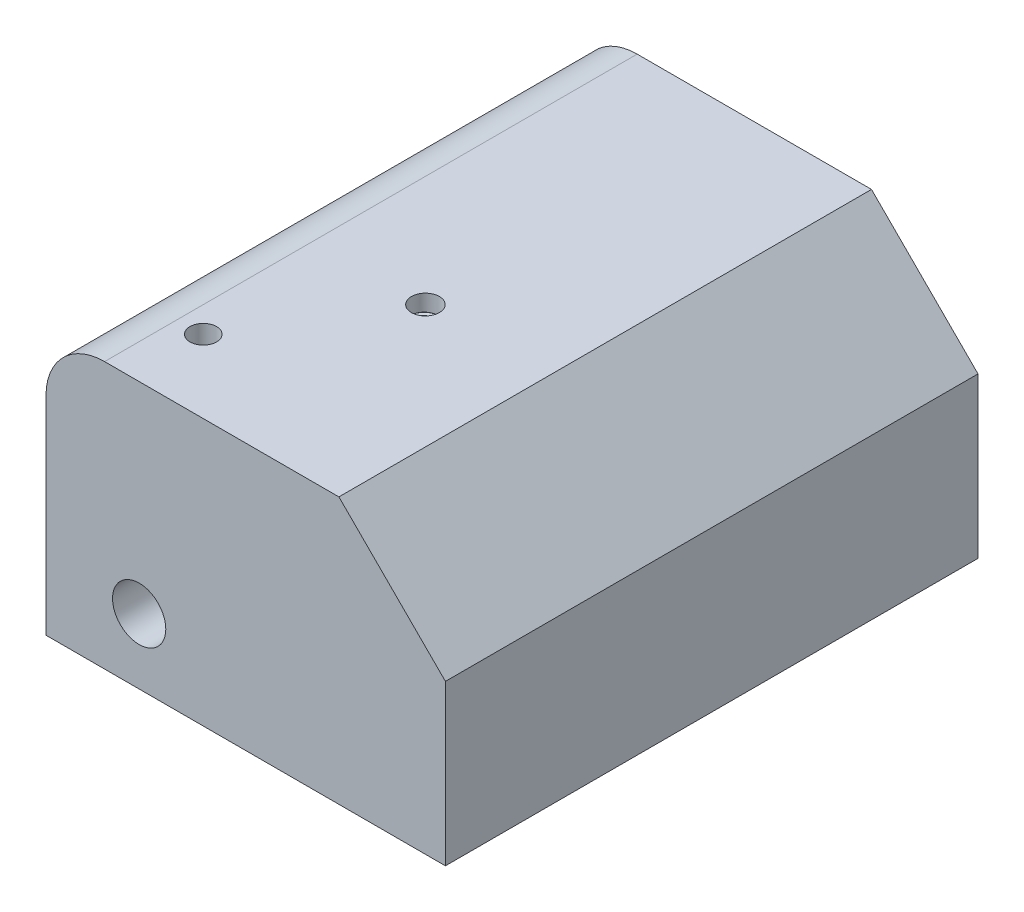
SolidWorks part; units mm, degrees
ref_plane "Front Plane" through (0, 0, 0) normal (0, 0, 1) x (1, 0, 0)
ref_plane "Top Plane" through (0, 0, 0) normal (0, 1, 0) x (1, 0, 0)
ref_plane "Right Plane" through (0, 0, 0) normal (1, 0, 0) x (0, 0, -1)
sketch "Sketch1" plane through (0, 0, 0) normal (0, 0, 1) x (1, 0, 0)
  line L5 (-40, 100) -> (0, 60)
  line L6 (0, 0) -> (-150, 0)
  line L7 (0, 0) -> (0, 60)
  line L8 (-40, 100) -> (-128, 100)
  line L9 (-150, 0) -> (-150, 78)
  arc A1 (-128, 100) -> (-150, 78) centre (-128, 78) ccw
  dimension "D3" = 150
  dimension "D1" = 22
  dimension "D2" = 100
  dimension "D4" = 40
  dimension "D5" = 40
extrude "Boss-Extrude1" add sketch "Sketch1" along normal mid plane 200
sketch "Sketch2" plane through (0, 0, 100) normal (0, 0, 1) x (1, 0, 0)
  point P0 (-115.0146, 24.4617)
  point P1 (0, 0)
sketch "Sketch3" plane through (0, 100, 0) normal (0, 1, 0) x (1, 0, 0)
  point P0 (-118.3591, -72.5794)
  point P1 (-86.3111, -21.2083)
  point P3 (-118.3591, -72.5794)
sketch "Sketch6" plane through (0, 0, 100) normal (0, 0, 1) x (1, 0, 0)
  point P0 (-115.0146, 24.4617)
hole_wizard "Hole1" positions "Sketch6" profile "Sketch7" legacy
sketch "Sketch7" plane through (-115.0146, 24.4617, 100) normal (1, 0, 0) x (0, -1, 0)
  line L0 (0, 0) -> (0, 20)
  line L1 (0, 20) -> (10, 20)
  line L2 (10, 20) -> (10, 0)
  line L3 (10, 0) -> (0, 0)
  line L4 (0, 110) -> (0, -10) construction
  dimension "Diameter" = 20
  dimension "Depth" = 20
sketch "Sketch10" plane through (0, 100, 0) normal (0, 1, 0) x (1, 0, 0)
  point P0 (-118.3591, -72.5794)
hole_wizard "Hole2" positions "Sketch10" profile "Sketch9" legacy
sketch "Sketch9" plane through (-118.3591, 100, 72.5794) normal (1, 0, 0) x (0, 0, 1)
  line L0 (0, 0) -> (0, 40)
  line L1 (0, 40) -> (5, 40)
  line L2 (5, 40) -> (5, 0)
  line L3 (5, 0) -> (0, 0)
  line L4 (0, 110) -> (0, -10) construction
  dimension "Diameter" = 10
  dimension "Depth" = 40
sketch "Sketch13" plane through (0, 100, 0) normal (0, 1, 0) x (1, 0, 0)
  point P0 (-86.3111, -21.2083)
hole_wizard "Hole3" positions "Sketch13" profile "Sketch12" legacy
sketch "Sketch12" plane through (-86.3111, 100, 21.2083) normal (1, 0, 0) x (0, 0, 1)
  line L0 (0, 0) -> (0, 30)
  line L1 (0, 30) -> (5.25, 30)
  line L2 (5.25, 30) -> (5.25, 0)
  line L3 (5.25, 0) -> (0, 0)
  line L4 (0, 110) -> (0, -10) construction
  dimension "Diameter" = 10.5
  dimension "Depth" = 30
thread "Thread1" pitch 1.5 method cut profile "Thread Profile1" start angle 0, offset 6, length 24, pitch 1.5, diameter 10.5
ref_plane "Plane1" through (-91.5611, 94, 21.2083) normal (0, 0, 1) x (-1, 0, 0)
sketch "Thread Profile1" plane through (-91.5611, 94, 21.2083) normal (0, 0, 1) x (-1, 0, 0)
  line L0 (0, 0) -> (0, 1.5) construction
  line L1 (0, 0) -> (0.8119, 0.4687)
  line L2 (0.8119, 0.4687) -> (0.8119, 0.6562)
  line L3 (0.8119, 0.6562) -> (0, 1.125)
  line L4 (0.8119, 0.5625) -> (0, 0.5625) construction
  line L11 (0, 0) -> (0, 1.125)
  point P2 (0, 0)
  dimension "Pitch" = 1.5
  dimension "Profile_Angle" = 60
  dimension "Profile_Land" = 0.1875
  dimension "Profile_Height" = 0.8119
